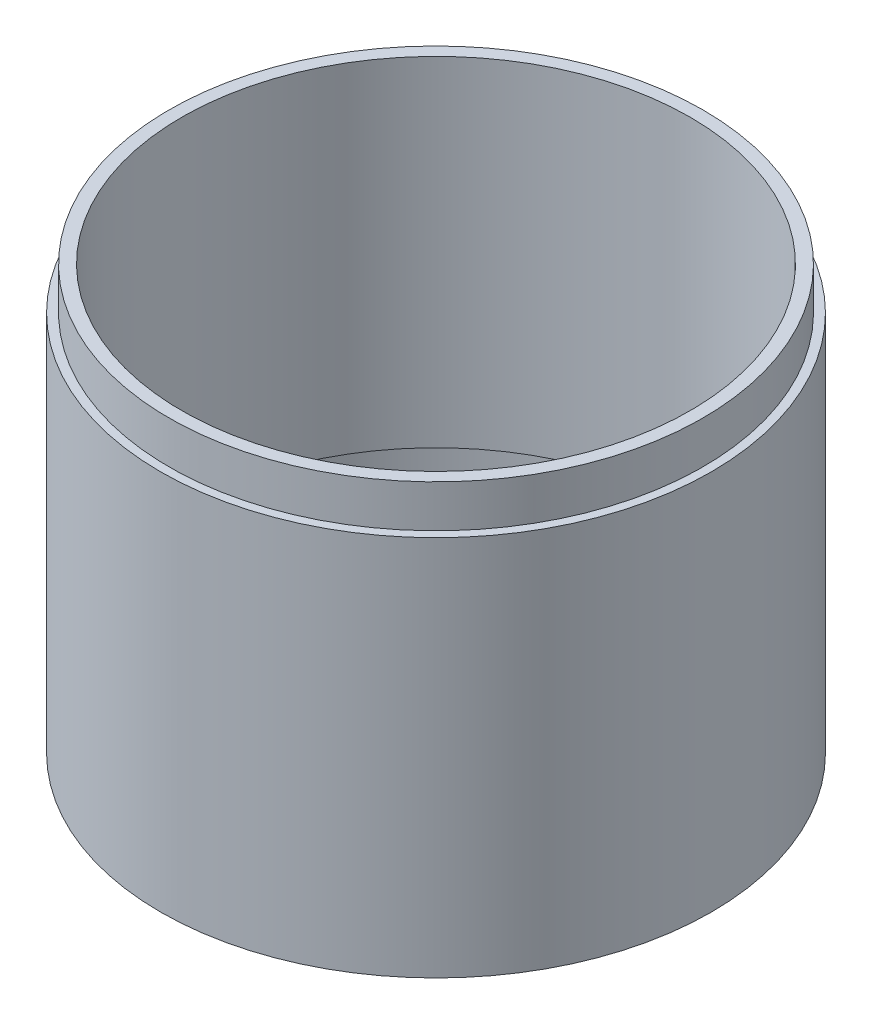
SolidWorks part; units mm, degrees
material "HYPALON"
ref_plane "Front Plane" through (0, 0, 0) normal (0, 0, 1) x (1, 0, 0)
ref_plane "Top Plane" through (0, 0, 0) normal (0, 1, 0) x (1, 0, 0)
ref_plane "Right Plane" through (0, 0, 0) normal (1, 0, 0) x (0, 0, -1)
sketch "Szkic1" plane through (0, 0, 0) normal (0, 0, 1) x (1, 0, 0)
  line L0 (0, 0) -> (-65, 0)
  line L1 (-65, 0) -> (-65, 20)
  line L2 (-62, 20) -> (-60, 20)
  line L3 (-60, 20) -> (-60, 100)
  line L4 (-62, 20) -> (-62, 0)
  line L5 (-60, 100) -> (-63, 100)
  line L7 (-65, 20) -> (-65, 90)
  line L8 (-65, 90) -> (-63, 90)
  line L9 (-63, 90) -> (-63, 100)
  line L13 (0, 0) -> (0, 22.4148)
  dimension "D1" = 65
  dimension "D2" = 20
  dimension "D3" = 62
  dimension "D4" = 100
  dimension "D7" = 2
  dimension "D8" = 10
  dimension "D13" = 2
revolve "Obrót1" add sketch "Szkic1" angle 360 about L13 region at (-62.5682, 51.5909, 0)
